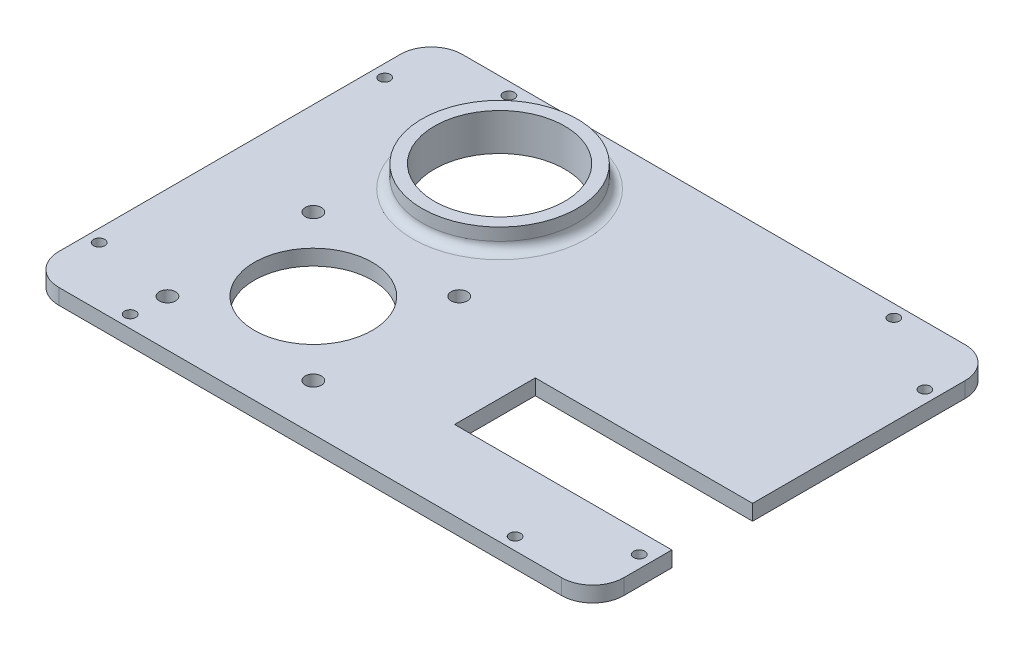
SolidWorks part; units mm, degrees
ref_plane "Front Plane" through (0, 0, 0) normal (0, 0, 1) x (1, 0, 0)
ref_plane "Top Plane" through (0, 0, 0) normal (0, 1, 0) x (1, 0, 0)
ref_plane "Right Plane" through (0, 0, 0) normal (1, 0, 0) x (0, 0, -1)
sketch "Sketch1" plane through (0, 0, 0) normal (0, 1, 0) x (1, 0, 0)
  line L20 (-28.5, 28.5) -> (28.5, 28.5)
  line L21 (-28.5, 28.5) -> (-28.5, -28.5)
  line L22 (-28.5, -28.5) -> (28.5, -28.5)
  line L23 (28.5, 28.5) -> (28.5, -28.5)
  line L24 (-28.5, 28.5) -> (28.5, -28.5) construction
  line L25 (-28.5, -28.5) -> (28.5, 28.5) construction
  line L26 (128.5, 13) -> (58.5, 13)
  line L27 (-43.5, 91.5) -> (118.5, 91.5)
  line L28 (-53.5, 81.5) -> (-53.5, -28.5)
  line L29 (-43.5, -38.5) -> (118.5, -38.5)
  line L30 (128.5, 81.5) -> (128.5, -28.5)
  line L31 (58.5, 13) -> (58.5, -13)
  line L32 (58.5, -13) -> (128.5, -13)
  line L33 (-10.5931, 81) -> (7.4203, 81) construction
  circle A12 centre (-23.5, 23.5) radius 2.6
  circle A13 centre (23.5, 23.5) radius 2.6
  circle A14 centre (23.5, -23.5) radius 2.6
  circle A15 centre (-23.5, -23.5) radius 2.6
  circle A16 centre (0, 0) radius 19
  circle A17 centre (0, 60) radius 21
  arc A18 (-43.5, 91.5) -> (-53.5, 81.5) centre (-43.5, 81.5) ccw
  arc A19 (118.5, 91.5) -> (128.5, 81.5) centre (118.5, 81.5) cw
  arc A20 (118.5, -38.5) -> (128.5, -28.5) centre (118.5, -28.5) ccw
  arc A21 (-53.5, -28.5) -> (-43.5, -38.5) centre (-43.5, -28.5) ccw
  point P0 (0, 0)
  point P7 (58.5, 0)
  point P37 (0, 0)
  dimension "D3" = 5.2
  dimension "D4" = 5
  dimension "D5" = 5
  dimension "D6" = 5.2
  dimension "D7" = 5
  dimension "D8" = 5
  dimension "D9" = 5.2
  dimension "D12" = 5.2
  dimension "D13" = 5
  dimension "D14" = 5
  dimension "D19" = 38
  dimension "D22" = 42
  dimension "D23" = 10
  dimension "D1" = 57
  dimension "D2" = 57
  dimension "D10" = 5
  dimension "D11" = 5
  dimension "D15" = 53.5
  dimension "D16" = 130
  dimension "D17" = 10
  dimension "D18" = 100
  dimension "D20" = 26
  dimension "D21" = 70
  dimension "D24" = 60
extrude "Boss-Extrude1" add sketch "Sketch1" along normal blind 5 contours L30 L27 L28 L29 L20 L23 L22 L21 | L23 L20 L21 L22 A15 A14 A13 A12 region at (0, 0, -27.6939) region at (41.6982, 0, -31.6354)
sketch "Sketch2" plane through (0, 5, 0) normal (0, 1, 0) x (1, 0, 0)
  circle A0 centre (0, 60) radius 25
  circle A1 centre (0, 60) radius 21
  point P4 (0, 0)
  dimension "D1" = 50
  dimension "D2" = 42
extrude "Boss-Extrude2" add sketch "Sketch2" along normal blind 7
fillet "Fillet1" radius 3 1 edges at (0, 5, -35)
sketch "Sketch4" plane through (0, 5, 0) normal (0, 1, 0) x (1, 0, 0)
  line L0 (-53.5, 26.5) -> (-37.2936, 26.5) construction
  line L1 (37.5, -49.0845) -> (37.5, -28.0576) construction
  line L2 (-43.5, -38.5) -> (118.5, -38.5) construction
  line L3 (-53.5, 81.5) -> (-53.5, -28.5) construction
  circle A0 centre (-49.5, -19.5) radius 1.8
  circle A1 centre (-24.5, -34.5) radius 1.8
  circle A8 centre (-24.5, 87.5) radius 1.8
  circle A9 centre (-49.5, 72.5) radius 1.8
  circle A10 centre (99.5, -34.5) radius 1.8
  circle A11 centre (124.5, -19.5) radius 1.8
  circle A12 centre (124.5, 72.5) radius 1.8
  circle A13 centre (99.5, 87.5) radius 1.8
  point P8 (0, 0)
  point P9 (-53.5, 26.5)
  point P10 (0, 0)
  point P11 (37.5, -38.5)
  point P24 (-31.704, -34.6122)
  dimension "D1" = 3.6
  dimension "D2" = 3.6
  dimension "D5" = 4
  dimension "D3" = 19
  dimension "D4" = 4
  dimension "D6" = 29
extrude "Cut-Extrude1" cut sketch "Sketch4" against normal through all
